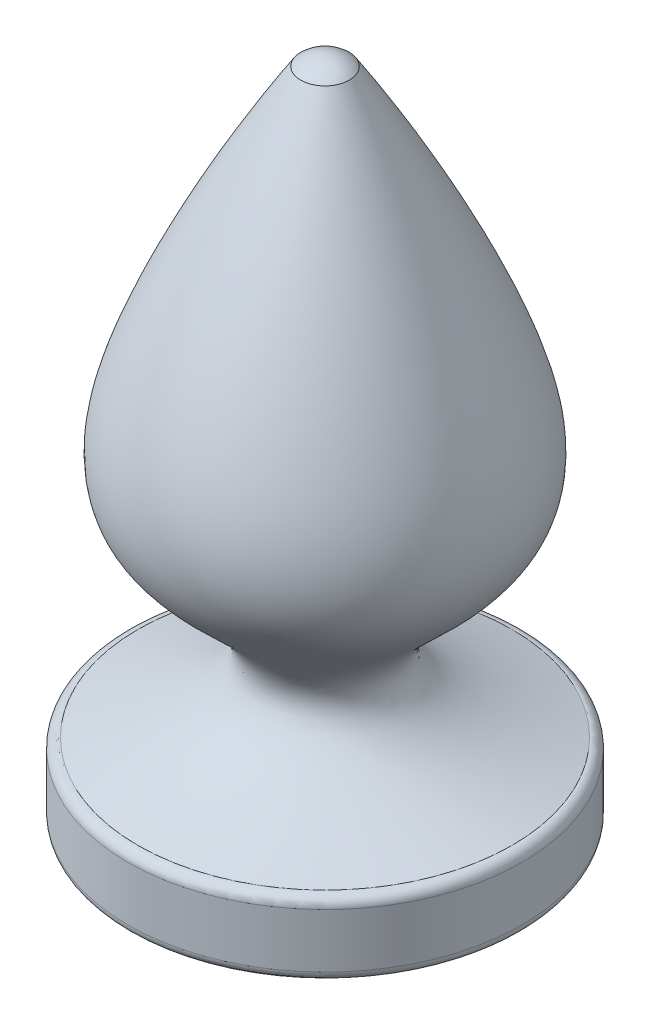
SolidWorks part; units mm, degrees
ref_plane "Front Plane" through (0, 0, 0) normal (0, 0, 1) x (1, 0, 0)
ref_plane "Top Plane" through (0, 0, 0) normal (0, 1, 0) x (1, 0, 0)
ref_plane "Right Plane" through (0, 0, 0) normal (1, 0, 0) x (0, 0, -1)
sketch "Sketch1" plane through (0, 0, 0) normal (0, 0, 1) x (1, 0, 0)
  line L0 (0, -40.5705) -> (0, 40.5705)
  line L2 (25.4, -32.3155) -> (25.4, -39.3005)
  line L3 (24.13, -40.5705) -> (0, -40.5705)
  line L6 (0, 40.5705) -> (0, 45.1545)
  arc A0 (3.1256, 43.9236) -> (0, 45.1545) centre (0, 40.5705) ccw
  arc A1 (25.4, -39.3005) -> (24.13, -40.5705) centre (24.13, -39.3005) cw
  arc A2 (24.13, -31.0455) -> (25.4, -32.3155) centre (24.13, -32.3155) cw
  spline S0 degree 3 poles (3.1256, 43.9236) (6.2293, 39.1286) (18.6626, 18.4795) (26.4058, -12.5101) (-5.6157, -21.4739) (24.13, -31.0455) knots 0 0 0 0 0.389546 0.60325 1 1 1 1
  point P2 (0, 0)
  point P4 (0, 0)
  point P5 (0, 0)
  point P8 (0, 0)
  point P17 (10.8906, -13.9365)
  point P19 (23.8232, -31.0455)
  point P20 (10.1612, -17.0365)
  point P21 (25.1143, -2.9952)
  point P22 (24.3849, -7.3718)
  point P23 (0, 0)
  point P24 (0, 0)
  point P25 (0, 0)
  point P26 (20.4848, -5.6177)
  dimension "D2" = 3.1256
  dimension "D3" = 1.27
  dimension "D1" = 4.5839
  dimension "D4" = 10.1612
  dimension "D5" = 19.05
  dimension "D6" = 20.4848
  dimension "D7" = 25.4
  dimension "D8" = 13.2755
  dimension "D9" = 40.5705
  dimension "D12" = 5.6177
  dimension "D13" = 17.0365
  dimension "D14" = 31.0455
revolve "Revolve1" add sketch "Sketch1" angle 360 about L0
